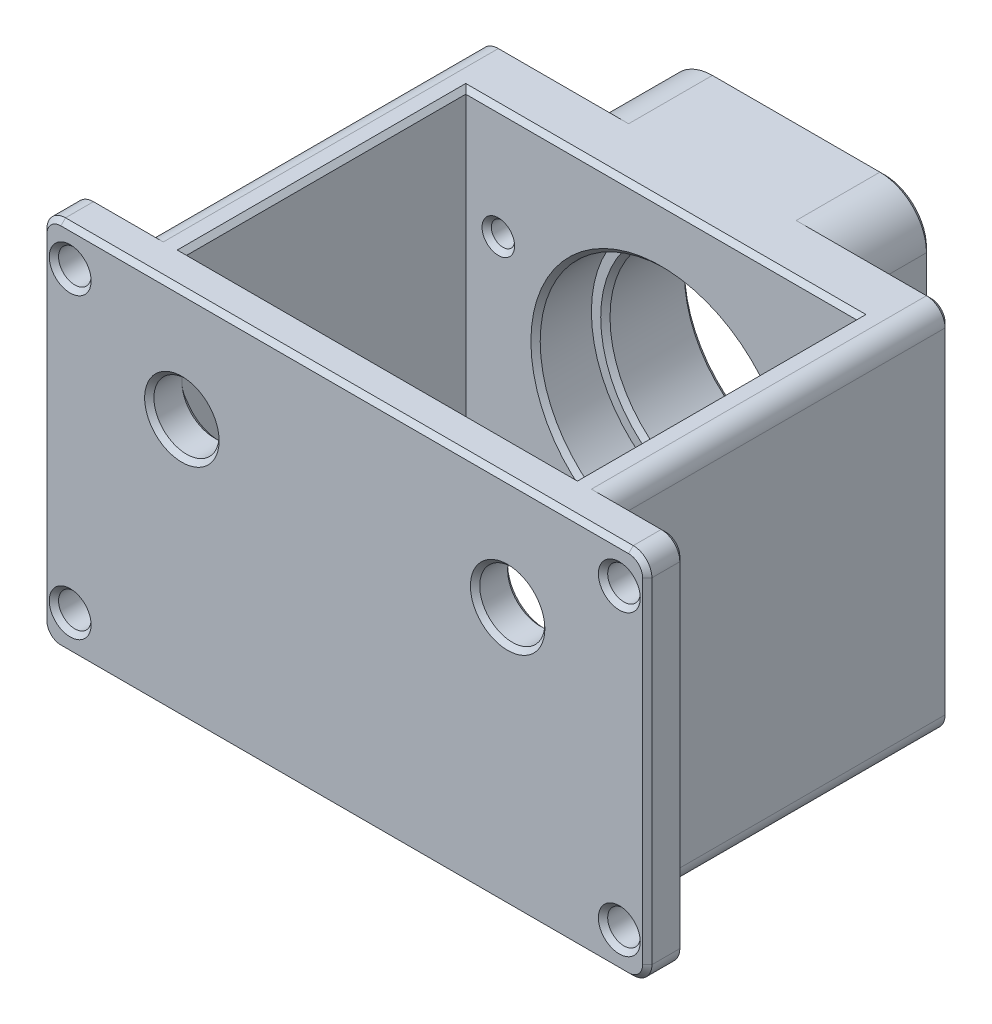
SolidWorks part; units mm, degrees
material "6061-T6 (GB)"
ref_plane "前视" through (0, 0, 0) normal (0, 0, 1) x (1, 0, 0)
ref_plane "上视" through (0, 0, 0) normal (0, 1, 0) x (1, 0, 0)
ref_plane "右视" through (0, 0, 0) normal (1, 0, 0) x (0, 0, -1)
sketch "草图1" plane through (0, 0, 0) normal (0, 0, 1) x (1, 0, 0)
  line L0 (0, 0) -> (0, 30.2327) construction
  line L1 (-25, -20) -> (25, -20)
  line L2 (-25, -20) -> (-25, 20)
  line L3 (-25, 20) -> (25, 20)
  line L4 (25, -20) -> (25, 20)
  line L5 (-25, -20) -> (25, 20) construction
  line L6 (-25, 20) -> (25, -20) construction
  line L7 (-25, 0) -> (25, 0) construction
  circle A0 centre (0, 0) radius 12
  circle A1 centre (-17.5, 8) radius 1.25
  circle A2 centre (17.5, 8) radius 1.25
  dimension "D1" = 40
  dimension "D3" = 24
  dimension "D4" = 35
  dimension "D5" = 2.5
  dimension "D6" = 8
  dimension "D2" = 50
extrude "凸台-拉伸1" add sketch "草图1" along normal blind 15
sketch "草图2" plane through (0, 0, 15) normal (0, 0, 1) x (1, 0, 0)
  line L0 (-25, -20) -> (25, -20) construction
  line L1 (-25, 20) -> (-21, 20)
  line L2 (-25, 20) -> (-25, -20)
  line L3 (-25, -20) -> (-21, -20)
  line L4 (-21, 20) -> (-21, -20)
  line L5 (0, 0) -> (0, 27.0284) construction
  line L6 (21, 20) -> (21, -20)
  line L7 (25, -20) -> (21, -20)
  line L8 (25, 20) -> (25, -20)
  line L9 (25, 20) -> (21, 20)
  dimension "D1" = 4
extrude "凸台-拉伸2" add sketch "草图2" along normal blind 30
sketch "草图3" plane through (0, 0, 45) normal (0, 0, 1) x (1, 0, 0)
  line L0 (-21, 20) -> (-25, 20) construction
  line L1 (-32.5, 20) -> (32.5, 20)
  line L2 (-32.5, 20) -> (-32.5, -20)
  line L3 (-32.5, -20) -> (32.5, -20)
  line L4 (32.5, 20) -> (32.5, -20)
  line L5 (21, -20) -> (25, -20) construction
  line L6 (0, 0) -> (0, 25.4704) construction
  line L7 (0, 0) -> (-35.1994, 0) construction
  circle A0 centre (-29.5, 16) radius 1.75
  circle A1 centre (29.5, 16) radius 1.75
  circle A2 centre (29.5, -16) radius 1.75
  circle A3 centre (-29.5, -16) radius 1.75
  circle A4 centre (-17.5, 8) radius 3.5
  circle A5 centre (17.5, 8) radius 3.5
  dimension "D2" = 3.5
  dimension "D3" = 3
  dimension "D4" = 59
  dimension "D5" = 4
  dimension "D6" = 32
  dimension "D7" = 7
  dimension "D1" = 65
extrude "凸台-拉伸3" add sketch "草图3" along normal blind 4
sketch "草图4" plane through (0, 0, 15) normal (0, 0, 1) x (1, 0, 0)
  circle A0 centre (0, 0) radius 13.5
  dimension "D1" = 27
extrude "切除-拉伸1" cut sketch "草图4" against normal offset from surface (6 mm away) 9 up to face at (-16.25, 8, 0)
sketch "草图5" plane through (0, 20, 0) normal (0, 1, 0) x (1, 0, 0)
  line L0 (0, 0) -> (0, -19.2179) construction
  line L1 (25, 0) -> (-25, 0) construction
  line L2 (14, 0) -> (14, -9)
  line L3 (-25, 0) -> (-14, 0)
  line L4 (-25, 0) -> (-25, -9)
  line L5 (-25, -9) -> (-14, -9)
  line L6 (-14, 0) -> (-14, -9)
  line L7 (25, -9) -> (14, -9)
  line L8 (25, 0) -> (25, -9)
  line L9 (25, 0) -> (14, 0)
  dimension "D1" = 28
  dimension "D2" = 9
extrude "切除-拉伸2" cut sketch "草图5" against normal through all
fillet "圆角2" radius 5 4 edges at (-14, -20, 4.5) (14, -20, 4.5) (14, 20, 4.5) (-14, 20, 4.5)
fillet "圆角1" radius 2 8 edges at (-25, 20, 27) (-25, -20, 27) (25, -20, 27) (25, 20, 27) (-32.5, 20, 47) (-32.5, -20, 47) (32.5, 20, 47) (32.5, -20, 47)
chamfer "倒角1" distance 0.5 angle 45 59 edges at (-31.25, -16, 49) (27.75, 16, 49) (31.9142, 19.4142, 49) (32.5, 0, 49) (31.9142, -19.4142, 49) (0, -20, 49) (-31.9142, -19.4142, 49) (-32.5, 0, 49) (-31.9142, 19.4142, 49) (0, 20, 49) (-27.75, 16, 49) (31.25, -16, 49) (0, -20, 0) (0, 20, 0) (12, 0, 0) (26.75, -20, 45) (31.9142, -19.4142, 45) (32.5, 0, 45) (31.9142, 19.4142, 45) (26.75, 20, 45) (-26.75, 20, 45) (-31.9142, 19.4142, 45) (-32.5, 0, 45) (-31.9142, -19.4142, 45) (-26.75, -20, 45) (0, 20, 45) (0, -20, 45) (-21, -20, 30) (21, -20, 30) (0, -20, 15) (0, 20, 15) (16.25, 8, 15) (-16.25, 8, 15) (18.75, 8, 9) (-16.25, 8, 9) (12.5355, -18.5355, 0) (14, 0, 0) (12.5355, 18.5355, 0) (-12.5355, 18.5355, 0) (-14, 0, 0) (-12.5355, -18.5355, 0) (-12, 0, 9) (16, 20, 9) (24.4142, 19.4142, 9) (25, 0, 9) (24.4142, -19.4142, 9) (16, -20, 9) (-16, -20, 9) (-24.4142, -19.4142, 9) (-25, 0, 9) (-24.4142, 19.4142, 9) (-16, 20, 9) (13.5, 0, 15) (14, 8, 49) (-14, 8, 49) (14, 8, 45) (-14, 8, 45) (21, 20, 30) (-21, 20, 30)
